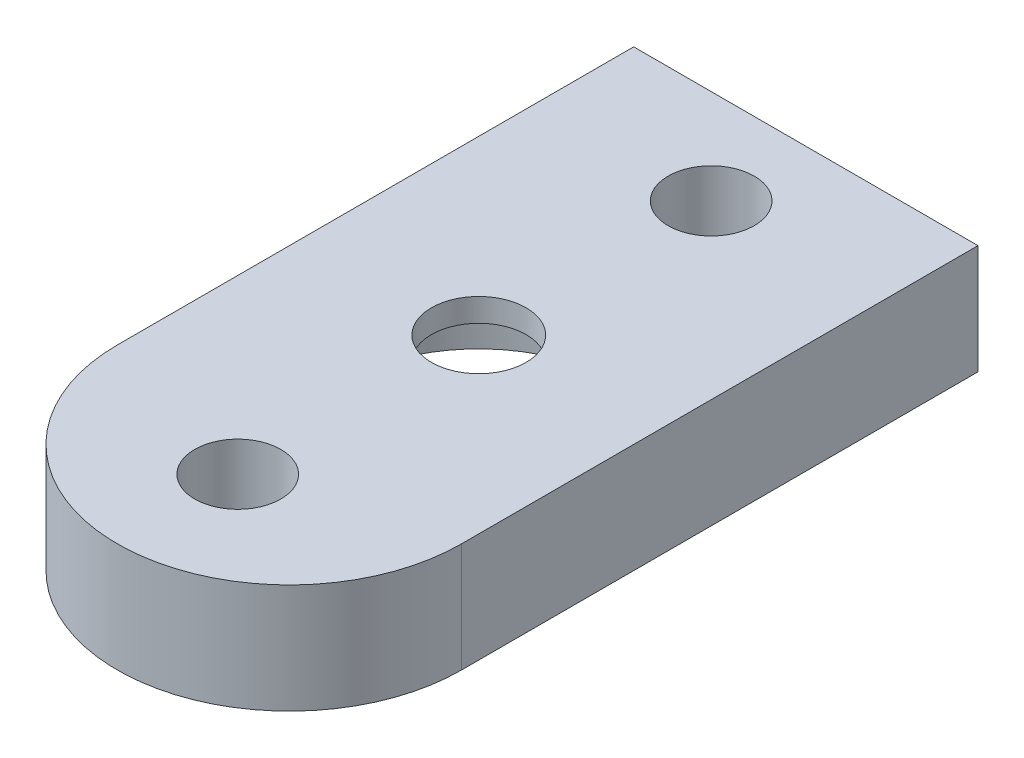
SolidWorks part; units mm, degrees
ref_plane "Front Plane" through (0, 0, 0) normal (0, 0, 1) x (1, 0, 0)
ref_plane "Top Plane" through (0, 0, 0) normal (0, 1, 0) x (1, 0, 0)
ref_plane "Right Plane" through (0, 0, 0) normal (1, 0, 0) x (0, 0, -1)
sketch "Sketch1" plane through (0, 0, 0) normal (0, 1, 0) x (1, 0, 0)
  line L9 (-10, 19) -> (-10, -11)
  line L10 (10, 19) -> (-10, 19)
  line L11 (10, -11) -> (10, 19)
  line L12 (-10, 19) -> (-10, -11)
  line L13 (10, 19) -> (-10, 19)
  line L14 (10, -11) -> (10, 19)
  arc A3 (-10, -11) -> (10, -11) centre (0, -11) ccw
  arc A4 (-10, -11) -> (10, -11) centre (0, -11) ccw
  point P6 (11.3197, -17.5)
  point P8 (0, 0)
  point P9 (10.4019, -17.6099)
  point P10 (-10, 19)
  point P12 (10, 16.4767)
  point P15 (10, -19)
  point P16 (0, 0)
  point P17 (0, 0)
  point P18 (0, 0)
  point P19 (0, 0)
  dimension "D1" = 0
extrude "Boss-Extrude1" add sketch "Sketch1" along normal blind 6.35
sketch "Sketch2" plane through (0, 0, 0) normal (0, -1, 0) x (1, 0, 0)
  circle A0 centre (0, 0) radius 8 construction
  circle A1 centre (0, 0) radius 8
extrude "Cut-Extrude1" cut sketch "Sketch2" against normal blind 5
sketch "Sketch3" plane through (0, 5, 0) normal (0, -1, 0) x (1, 0, 0)
  circle A0 centre (0, 0) radius 2.75 construction
  circle A1 centre (0, 0) radius 2.75
extrude "Cut-Extrude2" cut sketch "Sketch3" against normal through all
sketch "Sketch4" plane through (0, 0, 0) normal (0, -1, 0) x (1, 0, 0)
  circle A0 centre (0, 14) radius 2.5 construction
  circle A1 centre (0, 14) radius 2.5
  circle A2 centre (0, -13.5) radius 2.5 construction
  circle A3 centre (0, -13.5) radius 2.5
extrude "Cut-Extrude3" cut sketch "Sketch4" against normal through all
